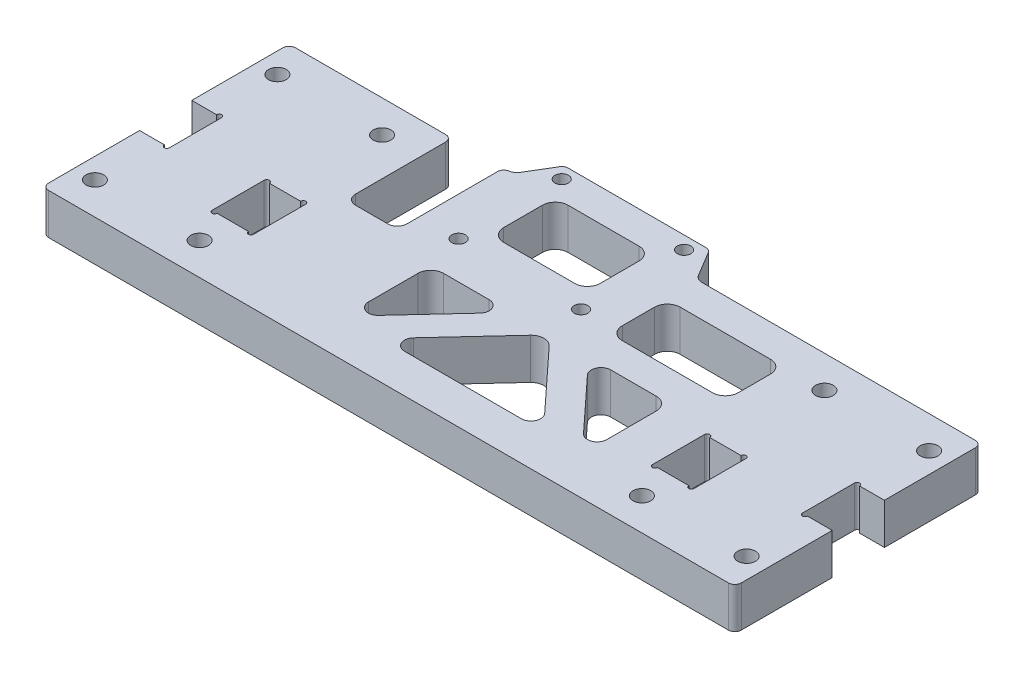
SolidWorks part; units mm, degrees
material "6061 Alloy"
ref_plane "Front Plane" through (0, 0, 0) normal (0, 0, 1) x (1, 0, 0)
ref_plane "Top Plane" through (0, 0, 0) normal (0, 1, 0) x (1, 0, 0)
ref_plane "Right Plane" through (0, 0, 0) normal (1, 0, 0) x (0, 0, -1)
sketch "Sketch1" plane through (0, 0, 0) normal (0, 1, 0) x (1, 0, 0)
  line L0 (107.5, 76.65) -> (107.5, 0) construction
  line L1 (0, 0) -> (215, 0)
  line L6 (32.7, 36.2) -> (32.7, 20)
  line L8 (45.6, 36.2) -> (45.6, 20)
  line L13 (0, 76.65) -> (69.5, 76.65)
  line L14 (69.5, 76.65) -> (75.5, 86.65)
  line L15 (75.5, 86.65) -> (120.5, 86.65)
  line L16 (120.5, 86.65) -> (126.5, 76.65)
  line L17 (126.5, 76.65) -> (215, 76.65)
  line L18 (32.7, 28.1) -> (45.6, 28.1) construction
  line L19 (34.3, 36.2) -> (44, 36.2)
  line L20 (34.3, 20) -> (44, 20)
  line L21 (182.3, 36.2) -> (182.3, 20)
  line L22 (180.7, 36.2) -> (171, 36.2)
  line L23 (169.4, 36.2) -> (169.4, 20)
  line L24 (180.7, 20) -> (171, 20)
  line L25 (9.28, 38.325) -> (0, 38.325) construction
  line L29 (9.28, 46.425) -> (9.28, 30.225)
  line L30 (7.68, 46.425) -> (0, 46.425)
  line L31 (7.68, 30.225) -> (0, 30.225)
  line L32 (0, 30.225) -> (0, 0)
  line L33 (0, 46.425) -> (0, 76.65)
  line L34 (205.72, 38.325) -> (215, 38.325) construction
  line L35 (215, 46.425) -> (215, 76.65)
  line L36 (215, 30.225) -> (215, 0)
  line L37 (207.32, 30.225) -> (215, 30.225)
  line L38 (207.32, 46.425) -> (215, 46.425)
  line L39 (205.72, 46.425) -> (205.72, 30.225)
  circle A0 centre (38.85, 66.65) radius 2.75
  circle A5 centre (38.85, 10) radius 2.75
  circle A6 centre (176.15, 66.65) radius 2.75
  circle A7 centre (176.15, 10) radius 2.75
  arc A8 (32.7, 36.2) -> (34.3, 36.2) centre (33.5, 36.2) cw
  arc A9 (45.6, 36.2) -> (44, 36.2) centre (44.8, 36.2) ccw
  arc A10 (32.7, 20) -> (34.3, 20) centre (33.5, 20) ccw
  arc A11 (45.6, 20) -> (44, 20) centre (44.8, 20) cw
  arc A12 (182.3, 20) -> (180.7, 20) centre (181.5, 20) cw
  arc A13 (182.3, 36.2) -> (180.7, 36.2) centre (181.5, 36.2) ccw
  arc A14 (169.4, 36.2) -> (171, 36.2) centre (170.2, 36.2) cw
  arc A15 (169.4, 20) -> (171, 20) centre (170.2, 20) ccw
  circle A16 centre (6.35, 10) radius 2.75
  circle A17 centre (6.35, 66.65) radius 2.75
  arc A18 (9.28, 30.225) -> (7.68, 30.225) centre (8.48, 30.225) cw
  arc A19 (9.28, 46.425) -> (7.68, 46.425) centre (8.48, 46.425) ccw
  arc A20 (205.72, 46.425) -> (207.32, 46.425) centre (206.52, 46.425) cw
  arc A21 (205.72, 30.225) -> (207.32, 30.225) centre (206.52, 30.225) ccw
  circle A22 centre (208.65, 66.65) radius 2.75
  circle A23 centre (208.65, 10) radius 2.75
  dimension "D12" = 5.5
  dimension "D16" = 5.5
  dimension "D17" = 0.8
  dimension "D18" = 0.8
  dimension "D19" = 0.8
  dimension "D20" = 0.8
  dimension "D21" = 5.5
  dimension "D22" = 5.5
  dimension "D27" = 0.8
  dimension "D1" = 215
  dimension "D2" = 76.65
  dimension "D5" = 61.9
  dimension "D6" = 12.9
  dimension "D4" = 10
  dimension "D7" = 6
  dimension "D8" = 38
  dimension "D10" = 45
  dimension "D11" = 16.2
  dimension "D14" = 6
  dimension "D13" = 10
  dimension "D15" = 10
  dimension "D24" = 38.325
  dimension "D25" = 16.2
extrude "Boss-Extrude1" add sketch "Sketch1" along normal blind 12.7
sketch "Sketch2" plane through (0, 12.7, 0) normal (0, 1, 0) x (1, 0, 0)
  line L1 (50.6, 85.2461) -> (66.6, 85.2461)
  line L2 (50.6, 85.2461) -> (50.6, 43.65)
  line L3 (50.6, 43.65) -> (66.6, 43.65)
  line L4 (66.6, 85.2461) -> (66.6, 43.65)
  line L5 (45.6, 20) -> (45.6, 36.2) construction
  line L12 (69.5, 76.65) -> (0, 76.65) construction
  dimension "D1" = 5
  dimension "D2" = 16
  dimension "D3" = 33
extrude "Cut-Extrude1" cut sketch "Sketch2" against normal through all
sketch "Sketch3" plane through (0, 12.7, 0) normal (0, 1, 0) x (1, 0, 0)
  line L1 (66.6, 43.65) -> (66.6, 76.65) construction
  line L2 (120.5, 86.65) -> (75.5, 86.65) construction
  circle A0 centre (78.6, 82.65) radius 2.1
  circle A1 centre (78.6, 50.65) radius 2.1
  circle A2 centre (116.6, 82.65) radius 2.1
  circle A3 centre (116.6, 50.65) radius 2.1
  dimension "D2" = 4.2
  dimension "D5" = 4.2
  dimension "D8" = 32
  dimension "D1" = 4
  dimension "D3" = 12
  dimension "D4" = 32
  dimension "D7" = 38
  dimension "D6" = 2
extrude "Cut-Extrude2" cut sketch "Sketch3" against normal through all
sketch "Sketch5" plane through (0, 12.7, 0) normal (0, 1, 0) x (1, 0, 0)
  line L2 (86.8013, 17.6174) -> (101.935, 33.9618)
  line L3 (99.7337, 39) -> (85.6, 39)
  line L8 (81.6, 35) -> (81.6, 19.6556)
  line L11 (0, 0) -> (215, 0) construction
  line L12 (66.6, 43.65) -> (66.6, 76.65) construction
  line L13 (115.665, 35.8302) -> (98.265, 17.0382)
  line L14 (118.6, 39) -> (118.6, 12) construction
  line L15 (100.4663, 12) -> (136.7337, 12)
  line L16 (121.535, 35.8302) -> (138.935, 17.0382)
  line L17 (137.4663, 39) -> (151.6, 39)
  line L18 (150.3987, 17.6174) -> (135.265, 33.9618)
  line L19 (155.6, 35) -> (155.6, 19.6556)
  line L20 (120.5, 86.65) -> (75.5, 86.65) construction
  line L21 (86.6, 76.65) -> (108.6, 76.65)
  line L22 (82.6, 72.65) -> (82.6, 60.65)
  line L23 (86.6, 56.65) -> (108.6, 56.65)
  line L24 (112.6, 72.65) -> (112.6, 60.65)
  line L25 (215, 76.65) -> (126.5, 76.65) construction
  line L26 (131.4, 66.65) -> (159.4, 66.65)
  line L27 (127.4, 62.65) -> (127.4, 52.65)
  line L28 (131.4, 48.65) -> (159.4, 48.65)
  line L29 (163.4, 62.65) -> (163.4, 52.65)
  line L31 (169.4, 36.2) -> (169.4, 20) construction
  arc A0 (121.535, 35.8302) -> (115.665, 35.8302) centre (118.6, 33.1125) ccw
  arc A1 (155.6, 35) -> (151.6, 39) centre (151.6, 35) ccw
  arc A2 (81.6, 35) -> (85.6, 39) centre (85.6, 35) cw
  arc A3 (112.6, 72.65) -> (108.6, 76.65) centre (108.6, 72.65) ccw
  arc A4 (108.6, 56.65) -> (112.6, 60.65) centre (108.6, 60.65) ccw
  arc A5 (82.6, 60.65) -> (86.6, 56.65) centre (86.6, 60.65) ccw
  arc A6 (82.6, 72.65) -> (86.6, 76.65) centre (86.6, 72.65) cw
  arc A7 (150.3987, 17.6174) -> (155.6, 19.6556) centre (152.6, 19.6556) ccw
  arc A8 (135.265, 33.9618) -> (137.4663, 39) centre (137.4663, 36) cw
  arc A9 (86.8013, 17.6174) -> (81.6, 19.6556) centre (84.6, 19.6556) cw
  arc A10 (136.7337, 12) -> (138.935, 17.0382) centre (136.7337, 15) ccw
  arc A11 (100.4663, 12) -> (98.265, 17.0382) centre (100.4663, 15) cw
  arc A12 (101.935, 33.9618) -> (99.7337, 39) centre (99.7337, 36) ccw
  arc A13 (163.4, 62.65) -> (159.4, 66.65) centre (159.4, 62.65) ccw
  arc A14 (159.4, 48.65) -> (163.4, 52.65) centre (159.4, 52.65) ccw
  arc A15 (127.4, 52.65) -> (131.4, 48.65) centre (131.4, 52.65) ccw
  arc A16 (127.4, 62.65) -> (131.4, 66.65) centre (131.4, 62.65) cw
  point P25 (155.6, 39)
  point P28 (81.6, 39)
  point P33 (112.6, 56.65)
  point P36 (82.6, 56.65)
  point P39 (82.6, 76.65)
  point P42 (155.6, 12)
  point P45 (130.6, 39)
  point P48 (81.6, 12)
  point P51 (143.6, 12)
  point P54 (93.6, 12)
  point P57 (106.6, 39)
  point P68 (163.4, 66.65)
  point P71 (163.4, 48.65)
  point P76 (127.4, 66.65)
  dimension "D11" = 4
  dimension "D12" = 3
  dimension "D13" = 3
  dimension "D14" = 3
  dimension "D19" = 4
  dimension "D1" = 12
  dimension "D2" = 27
  dimension "D3" = 12
  dimension "D4" = 15
  dimension "D5" = 25
  dimension "D6" = 25
  dimension "D7" = 10
  dimension "D8" = 16
  dimension "D9" = 20
  dimension "D10" = 30
  dimension "D15" = 10
  dimension "D16" = 18
  dimension "D17" = 6
  dimension "D18" = 36
extrude "Cut-Extrude3" cut sketch "Sketch5" against normal through all
fillet "Fillet1" radius 3 4 edges at (69.5, 6.35, -76.65) (66.6, 6.35, -43.65) (50.6, 6.35, -43.65) (126.5, 6.35, -76.65)
fillet "Fillet2" radius 2 8 edges at (0, 6.35, 0) (215, 6.35, 0) (215, 6.35, -76.65) (120.5, 6.35, -86.65) (75.5, 6.35, -86.65) (50.6, 6.35, -76.65) (66.6, 6.35, -76.65) (0, 6.35, -76.65)
equation "\"DriveMotorLength\"= 90mm"
equation "\"DriveMotorGap\"= 10mm"
equation "\"AluminumThickness\"= 0.5in"
equation "\"ChassisWidth\"= ( \"DriveMotorLength\" + \"AluminumThickness\" ) * 2 + \"DriveMotorGap\""
equation "\"RepeatMagnumHoleWidth\"= 19.05mm"
equation "\"MortiseWidth\"= 16mm"
equation "\"ChassisScrewThruHole\"= 5.5mm"
equation "\"D11@Sketch1\"=\"MortiseSlotWidth\""
equation "\"D12@Sketch1\"=\"ChassisScrewThruHole\""
equation "\"D16@Sketch1\"=\"ChassisScrewThruHole\""
equation "\"MortiseSlotWidth\"= 16.2mm"
equation "\"Dogbone\"= 0.8mm"
equation "\"D17@Sketch1\"=\"Dogbone\""
equation "\"D18@Sketch1\"=\"Dogbone\""
equation "\"D19@Sketch1\"=\"Dogbone\""
equation "\"D20@Sketch1\"=\"Dogbone\""
equation "\"D21@Sketch1\"=\"ChassisScrewThruHole\""
equation "\"D22@Sketch1\"=\"ChassisScrewThruHole\""
equation "\"D27@Sketch1\"=\"Dogbone\""
